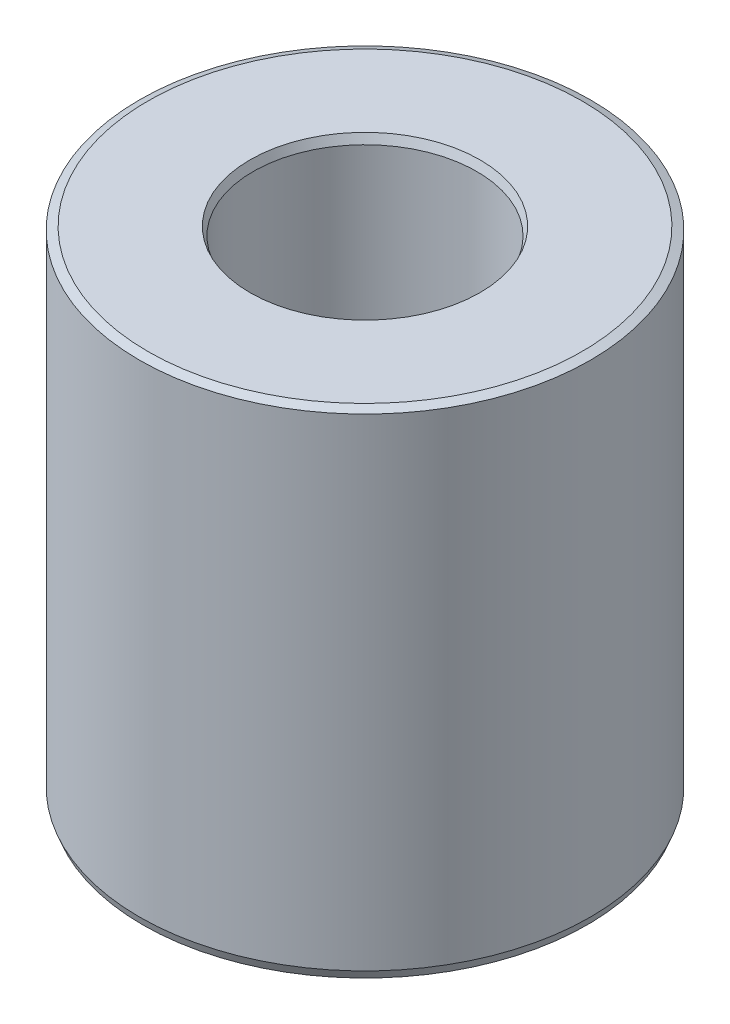
SolidWorks part; units mm, degrees
ref_plane "Front Plane" through (0, 0, 0) normal (0, 0, 1) x (1, 0, 0)
ref_plane "Top Plane" through (0, 0, 0) normal (0, 1, 0) x (1, 0, 0)
ref_plane "Right Plane" through (0, 0, 0) normal (1, 0, 0) x (0, 0, -1)
sketch "Sketch1" plane through (0, 0, 0) normal (0, 1, 0) x (1, 0, 0)
  circle A0 centre (0, 0) radius 47.5
  dimension "SLEEVE_OD" = 95
extrude "Boss-Extrude1" add sketch "Sketch1" along normal blind 104.0509
sketch "Sketch2" plane through (0, 0, 0) normal (0, 1, 0) x (1, 0, 0)
  circle A0 centre (0, 0) radius 23.5491
  dimension "BORE_D" = 47.0983
extrude "Cut-Extrude1" cut sketch "Sketch2" along normal through all
chamfer "Chamfer1" distance 0.6844 angle 68.969 4 edges at (0, 104.0509, 23.5491) (0, 0, 23.5491) (0, 0, 47.5) (0, 104.0509, 47.5) first distance on face at (0, 104.0509, 23.5491) first distance on face at (0, 0, 23.5491) first distance on face at (0, 104.0509, 47.5)
